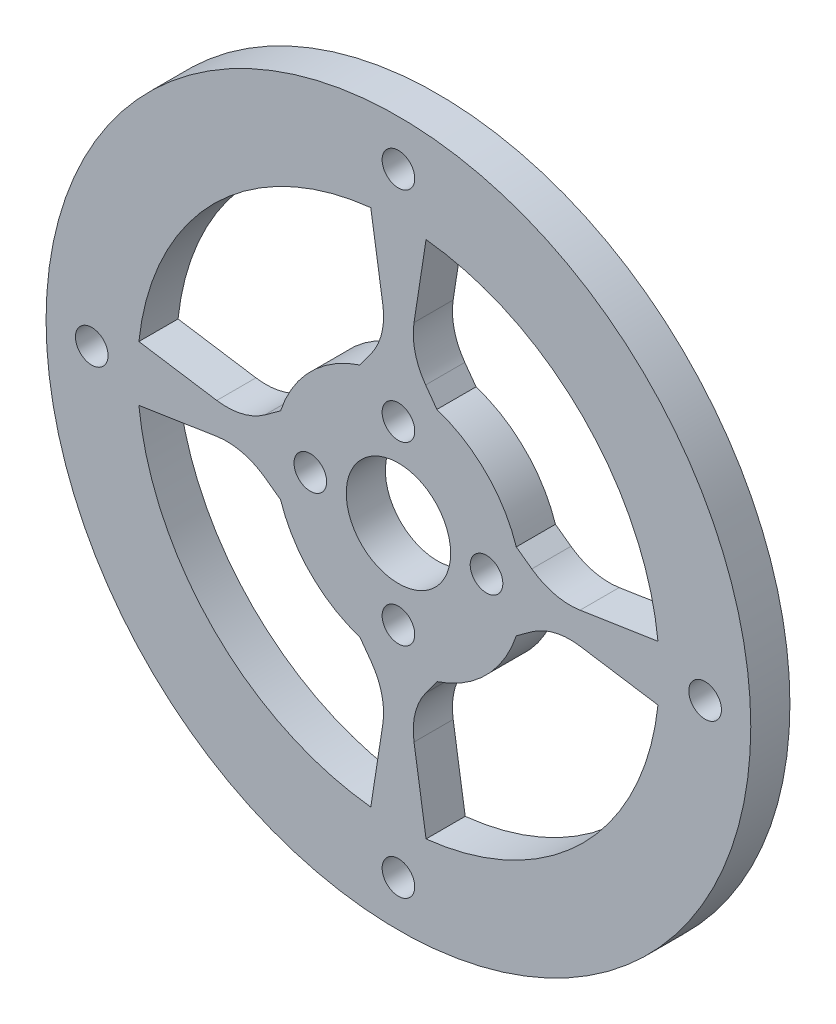
SolidWorks part; units mm, degrees
ref_plane "Front Plane" through (0, 0, 0) normal (0, 0, 1) x (1, 0, 0)
ref_plane "Top Plane" through (0, 0, 0) normal (0, 1, 0) x (1, 0, 0)
ref_plane "Right Plane" through (0, 0, 0) normal (1, 0, 0) x (0, 0, -1)
sketch "Sketch1" plane through (0, 0, 0) normal (0, 0, 1) x (1, 0, 0)
  line L0 (55, 0) -> (-55, 0) construction
  circle A0 centre (0, 0) radius 4
  circle A1 centre (0, 0) radius 9.5
  circle A2 centre (0, 0) radius 6.75 construction
  circle A3 centre (0, 0) radius 27
  circle A4 centre (0, 0) radius 20
  circle A5 centre (0, 0) radius 23.5 construction
  circle A6 centre (0, 6.75) radius 1.25
  circle A7 centre (0, 23.5) radius 1.25
  circle A9 centre (-23.5, 0) radius 1.25
  circle A10 centre (-6.75, 0) radius 1.25
  circle A11 centre (0, -23.5) radius 1.25
  circle A12 centre (0, -6.75) radius 1.25
  circle A13 centre (23.5, 0) radius 1.25
  circle A14 centre (6.75, 0) radius 1.25
  dimension "D1" = 8
  dimension "D2" = 19
  dimension "D3" = 2.75
  dimension "D4" = 54
  dimension "D5" = 40
  dimension "D6" = 3.5
  dimension "D7" = 2.5
  dimension "D8" = 2.5
  dimension "D9" = 4
extrude "Boss-Extrude1" add sketch "Sketch1" along normal blind 3 contours A3 A13 A11 A9 A7 A4 | A1 A14 A12 A10 A6 A0 region at (-9.2313, 0, 0) region at (-26.2363, 0, 0)
sketch "Sketch2" plane through (0, 0, 0) normal (0, 0, 1) x (1, 0, 0)
  line L0 (-2.1175, 19.8876) -> (-1.1948, 13.9182)
  line L1 (-2.0858, 10.2228) -> (-2.9484, 9.0309)
  line L2 (-2.9484, 9.0309) -> (2.9484, 9.0309)
  line L3 (0, -1.65) -> (0, 1.65) construction
  line L4 (0, 9.0309) -> (0, 20.2149)
  line L5 (0, 20.2149) -> (-2.1175, 19.8876)
  line L6 (0, 20.2149) -> (2.1175, 19.8876)
  line L7 (2.0858, 10.2228) -> (2.9484, 9.0309)
  line L8 (2.1175, 19.8876) -> (1.1948, 13.9182)
  line L9 (19.8876, 2.1175) -> (13.9182, 1.1948)
  line L10 (20.2149, 0) -> (19.8876, 2.1175)
  line L11 (19.8876, -2.1175) -> (13.9182, -1.1948)
  line L12 (20.2149, 0) -> (19.8876, -2.1175)
  line L13 (10.2228, -2.0858) -> (9.0309, -2.9484)
  line L14 (9.0309, 2.9484) -> (9.0309, -2.9484)
  line L15 (10.2228, 2.0858) -> (9.0309, 2.9484)
  line L16 (2.1175, -19.8876) -> (1.1948, -13.9182)
  line L17 (0, -20.2149) -> (2.1175, -19.8876)
  line L18 (-2.1175, -19.8876) -> (-1.1948, -13.9182)
  line L19 (0, -20.2149) -> (-2.1175, -19.8876)
  line L20 (-2.0858, -10.2228) -> (-2.9484, -9.0309)
  line L21 (2.9484, -9.0309) -> (-2.9484, -9.0309)
  line L22 (2.0858, -10.2228) -> (2.9484, -9.0309)
  line L23 (-19.8876, -2.1175) -> (-13.9182, -1.1948)
  line L24 (-20.2149, 0) -> (-19.8876, -2.1175)
  line L25 (-19.8876, 2.1175) -> (-13.9182, 1.1948)
  line L26 (-20.2149, 0) -> (-19.8876, 2.1175)
  line L27 (-10.2228, 2.0858) -> (-9.0309, 2.9484)
  line L28 (-9.0309, -2.9484) -> (-9.0309, 2.9484)
  line L29 (-10.2228, -2.0858) -> (-9.0309, -2.9484)
  circle A0 centre (0, 0) radius 20 construction
  circle A1 centre (0, 0) radius 9.5 construction
  arc A2 (-1.1948, 13.9182) -> (-2.0858, 10.2228) centre (-6.1361, 13.1544) cw
  arc A3 (1.1948, 13.9182) -> (2.0858, 10.2228) centre (6.1361, 13.1544) ccw
  arc A4 (13.9182, 1.1948) -> (10.2228, 2.0858) centre (13.1544, 6.1361) cw
  arc A5 (13.9182, -1.1948) -> (10.2228, -2.0858) centre (13.1544, -6.1361) ccw
  arc A6 (1.1948, -13.9182) -> (2.0858, -10.2228) centre (6.1361, -13.1544) cw
  arc A7 (-1.1948, -13.9182) -> (-2.0858, -10.2228) centre (-6.1361, -13.1544) ccw
  arc A8 (-13.9182, -1.1948) -> (-10.2228, -2.0858) centre (-13.1544, -6.1361) cw
  arc A9 (-13.9182, 1.1948) -> (-10.2228, 2.0858) centre (-13.1544, 6.1361) ccw
  point P19 (0, 0)
  dimension "D1" = 5
  dimension "D2" = 4
extrude "Boss-Extrude2" add sketch "Sketch2" along normal up to surface (3 mm away) contours A9 L25 L26 L24 L23 A8 L29 L28 L27 | L6 L8 A3 L7 L2 L1 A2 L0 L5 | L11 A5 L13 L14 L15 A4 L9 L10 L12 | L16 A6 L22 L21 L20 A7 L18 L19 L17 region at (-14.5163, 0, 0) up to face at (24.75, 0, 3)
ref_axis "Axis1" through (0, 0, -0.15) along (0, 0, 1)
